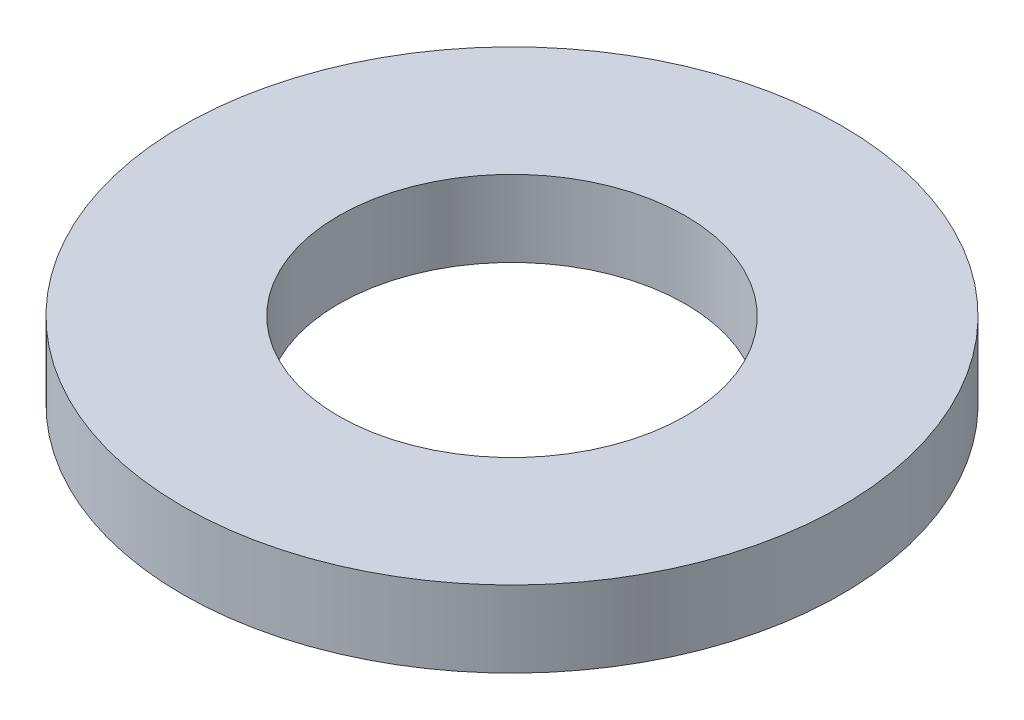
SolidWorks part; units mm, degrees
ref_plane "Front Plane" through (0, 0, 0) normal (0, 0, 1) x (1, 0, 0)
ref_plane "Top Plane" through (0, 0, 0) normal (0, 1, 0) x (1, 0, 0)
ref_plane "Right Plane" through (0, 0, 0) normal (1, 0, 0) x (0, 0, -1)
sketch "Sketch1" plane through (0, 0, 0) normal (0, 1, 0) x (1, 0, 0)
  circle A0 centre (0, 0) radius 95
  dimension "FLANGE_OD" = 190
extrude "Boss-Extrude1" add sketch "Sketch1" along normal blind 22
sketch "Sketch2" plane through (0, 0, 0) normal (0, 1, 0) x (1, 0, 0)
  circle A0 centre (0, 0) radius 50
  dimension "BORE_D" = 100
extrude "Cut-Extrude1" cut sketch "Sketch2" along normal through all
sketch "Sketch3" plane through (0, 22, 0) normal (0, 1, 0) x (1, 0, 0)
  circle A0 centre (0, 0) radius 30.6278 construction
  circle A1 centre (-30.6278, 0) radius 1.5788
  dimension "BOLT_D" = 3.1575
  dimension "BOLT_PCD" = 61.2556
extrude "Cut-Extrude2" cut sketch "Sketch3" against normal blind 20.3106 rebuild error yes
pattern_circular "CirPattern1" count 8 over 360 rebuild error yes
